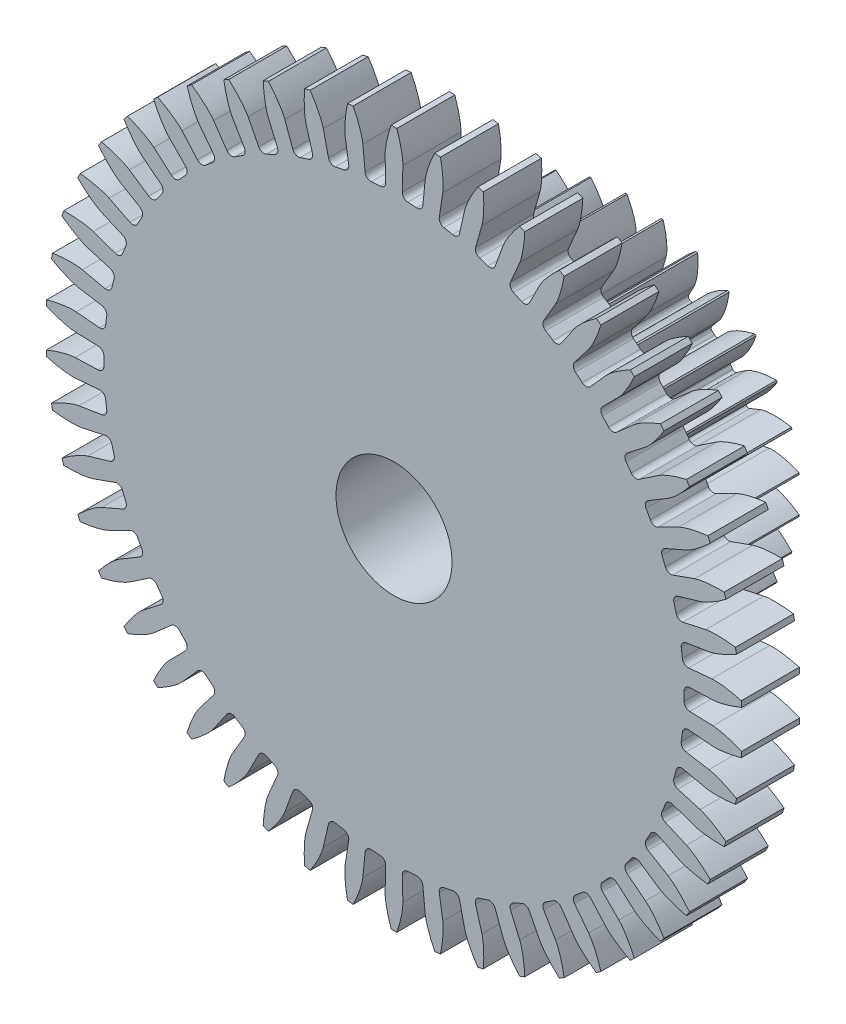
SolidWorks part; units mm, degrees
ref_plane "Piano frontale" through (0, 0, 0) normal (0, 0, 1) x (1, 0, 0)
ref_plane "Piano superiore" through (0, 0, 0) normal (0, 1, 0) x (1, 0, 0)
ref_plane "Piano destro" through (0, 0, 0) normal (1, 0, 0) x (0, 0, -1)
sketch "Schizzo1" plane through (0, 0, 0) normal (0, 0, 1) x (1, 0, 0)
  circle A0 centre (0, 0) radius 6
  circle A2 centre (0, 0) radius 1
  dimension "D1" = 2
  dimension "D2" = 12
extrude "Estrusione-Estrusione1" add sketch "Schizzo1" along normal blind 1
sketch "Schizzo2" plane through (0, 0, 1) normal (0, 0, 1) x (1, 0, 0)
  line L0 (0, 0) -> (6, 0) construction
  line L7 (6, 0) -> (0, 0) construction
  line L8 (0, 0) -> (5.4966, 0.1919) construction
  line L9 (0, 0) -> (5.4966, -0.1919) construction
  line L10 (8.3142, -2.6251) -> (8.3142, 2.6251)
  line L11 (5.4966, -0.1919) -> (5.0959, -0.178)
  line L12 (5.4966, 0.1919) -> (5.0959, 0.178)
  circle A1 centre (0, 0) radius 6 construction
  arc A7 (5.4966, -0.1919) -> (5.4966, 0.1919) centre (0, 0) ccw construction
  arc A8 (4.9994, -0.0765) -> (4.9994, 0.0765) centre (0, 0) ccw
  arc A9 (4.9994, 0.0765) -> (5.0959, 0.178) centre (5.0994, 0.078) cw
  arc A10 (4.9994, -0.0765) -> (5.0959, -0.178) centre (5.0994, -0.078) ccw
  spline S0 degree 4 poles (5.4966, 0.1919) (5.5023, 0.1921) (5.5182, 0.1931) (5.5482, 0.1964) (5.5968, 0.204) (5.6583, 0.2168) (5.737, 0.2371) (5.8288, 0.2655) (5.9283, 0.3015) (6.0349, 0.3457) (6.1398, 0.3943) (6.2427, 0.4469) (6.3438, 0.5029) (6.4642, 0.5749) (6.6058, 0.667) (6.7668, 0.783) (6.9438, 0.9241) (7.1177, 1.0777) (7.2834, 1.2368) (7.444, 1.4063) (7.5946, 1.5765) (7.7436, 1.7616) (7.8773, 1.9368) (8.0184, 2.1419) (8.1298, 2.3099) (8.2671, 2.5404) (8.3452, 2.679) (8.4332, 2.8442) (8.4704, 2.919) (8.4934, 2.9651) knots 0 0 0 0 0 0.005377 0.015084 0.028532 0.04661 0.064855 0.092111 0.119476 0.146842 0.174209 0.201575 0.228941 0.256307 0.307035 0.361767 0.4165 0.471232 0.525964 0.580697 0.635429 0.690161 0.744894 0.799626 0.854358 0.909091 0.954545 1 1 1 1 1 construction
  spline S1 degree 4 poles (5.4966, 0.1919) (5.5023, 0.1921) (5.5182, 0.1931) (5.5482, 0.1964) (5.5968, 0.204) (5.6583, 0.2168) (5.737, 0.2371) (5.8288, 0.2655) (5.9283, 0.3015) (6.0349, 0.3457) (6.1398, 0.3943) (6.2427, 0.4469) (6.3438, 0.5029) (6.4642, 0.5749) (6.6058, 0.667) (6.7668, 0.783) (6.9438, 0.9241) (7.1177, 1.0777) (7.2834, 1.2368) (7.444, 1.4063) (7.5946, 1.5765) (7.7436, 1.7616) (7.8773, 1.9368) (8.0184, 2.1419) (8.1298, 2.3099) (8.2373, 2.4904) (8.2885, 2.5792) (8.3142, 2.6251) knots 0 0 0 0 0 0.005377 0.015084 0.028532 0.04661 0.064855 0.092111 0.119476 0.146842 0.174209 0.201575 0.228941 0.256307 0.307035 0.361767 0.4165 0.471232 0.525964 0.580697 0.635429 0.690161 0.744894 0.799626 0.854358 0.909091 0.909091 0.909091 0.909091 0.909091
  spline S2 degree 4 poles (5.4966, -0.1919) (5.5023, -0.1921) (5.5182, -0.1931) (5.5482, -0.1964) (5.5968, -0.204) (5.6583, -0.2168) (5.737, -0.2371) (5.8288, -0.2655) (5.9283, -0.3015) (6.0349, -0.3457) (6.1398, -0.3943) (6.2427, -0.4469) (6.3438, -0.5029) (6.4642, -0.5749) (6.6058, -0.667) (6.7668, -0.783) (6.9438, -0.9241) (7.1177, -1.0777) (7.2834, -1.2368) (7.444, -1.4063) (7.5946, -1.5765) (7.7436, -1.7616) (7.8773, -1.9368) (8.0184, -2.1419) (8.1298, -2.3099) (8.2373, -2.4904) (8.2885, -2.5792) (8.3142, -2.6251) knots 0 0 0 0 0 0.005377 0.015084 0.028532 0.04661 0.064855 0.092111 0.119476 0.146842 0.174209 0.201575 0.228941 0.256307 0.307035 0.361767 0.4165 0.471232 0.525964 0.580697 0.635429 0.690161 0.744894 0.799626 0.854358 0.909091 0.909091 0.909091 0.909091 0.909091
  point P5 (4.997, 0.1745)
  point P17 (4.997, -0.1745)
  dimension "D3" = 2
  dimension "D1" = 11
  dimension "D4" = 2
  dimension "D5" = 0.1
  dimension "D2" = 10
  dimension "D6" = 0.1
extrude "Taglio-Estrusione1" cut sketch "Schizzo2" against normal up to next
pattern_circular "RipetizioneCircolare1" count 50 over 360 about axis through (0, 0, 1) along (0, 0, 1) of "Taglio-Estrusione1"
sketch "Schizzo3" plane through (0, 0, 0) normal (0, 0, -1) x (-1, 0, 0)
  circle A0 centre (0, 0) radius 1 construction
  circle A1 centre (0, 0) radius 1
  circle A2 centre (0, 0) radius 3
  dimension "D1" = 6
extrude "Estrusione-Estrusione2" add sketch "Schizzo3" along normal blind 3
sketch "Schizzo4" plane through (0, 0, -3) normal (0, 0, -1) x (-1, 0, 0)
  line L0 (0, 0) -> (2.5, 0) construction
  line L1 (0, 0) -> (2.4985, 0.0872) construction
  line L2 (0, 0) -> (2.4985, -0.0872) construction
  line L3 (3.706, -1.13) -> (3.706, 1.13)
  line L4 (2.4985, -0.0872) -> (2.2981, -0.0802)
  line L5 (2.4985, 0.0872) -> (2.2981, 0.0802)
  arc A0 (2.4985, -0.0872) -> (2.4985, 0.0872) centre (0, 0) ccw construction
  arc A1 (2.2498, -0.0296) -> (2.2498, 0.0296) centre (0, 0) ccw
  arc A3 (2.2498, 0.0296) -> (2.2981, 0.0802) centre (2.2998, 0.0303) cw
  arc A4 (2.2498, -0.0296) -> (2.2981, -0.0802) centre (2.2998, -0.0303) ccw
  spline S0 degree 4 poles (2.4985, 0.0872) (2.5009, 0.0873) (2.5077, 0.0877) (2.5206, 0.0892) (2.5414, 0.0924) (2.5798, 0.1004) (2.6253, 0.1133) (2.6758, 0.131) (2.7292, 0.1532) (2.7741, 0.174) (2.8182, 0.1965) (2.8615, 0.2205) (2.9131, 0.2514) (2.9738, 0.2909) (3.0428, 0.3406) (3.1187, 0.401) (3.1932, 0.4669) (3.2642, 0.5351) (3.3331, 0.6077) (3.3976, 0.6806) (3.4615, 0.76) (3.5188, 0.8351) (3.5792, 0.9229) (3.627, 0.9949) (3.6858, 1.0937) (3.7193, 1.1531) (3.757, 1.2239) (3.7729, 1.256) (3.7828, 1.2757) knots 0 0 0 0 0 0.005377 0.015084 0.028532 0.04661 0.092111 0.119476 0.146842 0.174209 0.201575 0.228941 0.256307 0.307035 0.361767 0.4165 0.471232 0.525964 0.580697 0.635429 0.690161 0.744894 0.799626 0.854358 0.909091 0.954545 1 1 1 1 1 construction
  spline S1 degree 4 poles (2.4985, 0.0872) (2.5009, 0.0873) (2.5077, 0.0877) (2.5206, 0.0892) (2.5414, 0.0924) (2.5798, 0.1004) (2.6253, 0.1133) (2.6758, 0.131) (2.7292, 0.1532) (2.7741, 0.174) (2.8182, 0.1965) (2.8615, 0.2205) (2.9131, 0.2514) (2.9738, 0.2909) (3.0428, 0.3406) (3.1187, 0.401) (3.1932, 0.4669) (3.2642, 0.5351) (3.3331, 0.6077) (3.3976, 0.6806) (3.4615, 0.76) (3.5188, 0.8351) (3.5792, 0.9229) (3.627, 0.9949) (3.673, 1.0723) (3.695, 1.1104) (3.706, 1.13) knots 0 0 0 0 0 0.005377 0.015084 0.028532 0.04661 0.092111 0.119476 0.146842 0.174209 0.201575 0.228941 0.256307 0.307035 0.361767 0.4165 0.471232 0.525964 0.580697 0.635429 0.690161 0.744894 0.799626 0.854358 0.909091 0.909091 0.909091 0.909091 0.909091
  spline S2 degree 4 poles (2.4985, -0.0872) (2.5009, -0.0873) (2.5077, -0.0877) (2.5206, -0.0892) (2.5414, -0.0924) (2.5798, -0.1004) (2.6253, -0.1133) (2.6758, -0.131) (2.7292, -0.1532) (2.7741, -0.174) (2.8182, -0.1965) (2.8615, -0.2205) (2.9131, -0.2514) (2.9738, -0.2909) (3.0428, -0.3406) (3.1187, -0.401) (3.1932, -0.4669) (3.2642, -0.5351) (3.3331, -0.6077) (3.3976, -0.6806) (3.4615, -0.76) (3.5188, -0.8351) (3.5792, -0.9229) (3.627, -0.9949) (3.673, -1.0723) (3.695, -1.1104) (3.706, -1.13) knots 0 0 0 0 0 0.005377 0.015084 0.028532 0.04661 0.092111 0.119476 0.146842 0.174209 0.201575 0.228941 0.256307 0.307035 0.361767 0.4165 0.471232 0.525964 0.580697 0.635429 0.690161 0.744894 0.799626 0.854358 0.909091 0.909091 0.909091 0.909091 0.909091
  point P12 (2.2486, 0.0785)
  point P16 (2.2486, -0.0785)
  dimension "D2" = 5
  dimension "D1" = 4.5
  dimension "D5" = 0.05
  dimension "D6" = 0.05
  dimension "D3" = 2
  dimension "D4" = 178
extrude "Taglio-Estrusione2" cut sketch "Schizzo4" against normal up to surface (3 mm away) up to face at (0, 0, 0)
pattern_circular "RipetizioneCircolare2" count 30 over 360 of "Taglio-Estrusione2"
